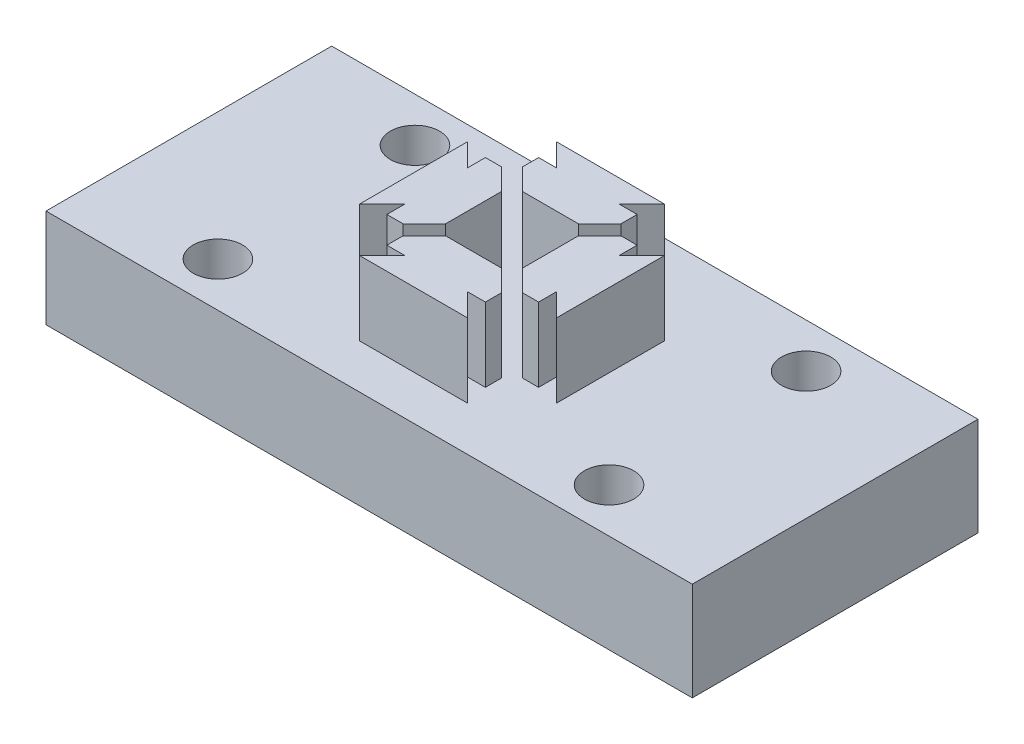
SolidWorks part; units mm, degrees
ref_plane "Front Plane" through (0, 0, 0) normal (0, 0, 1) x (1, 0, 0)
ref_plane "Top Plane" through (0, 0, 0) normal (0, 1, 0) x (1, 0, 0)
ref_plane "Right Plane" through (0, 0, 0) normal (1, 0, 0) x (0, 0, -1)
sketch "Sketch1" plane through (0, 0, 0) normal (0, 1, 0) x (1, 0, 0)
  line L0 (0, 14.5) -> (0, -14.5) construction
  line L1 (-32.8, -14.5) -> (32.8, -14.5)
  line L2 (-32.8, -14.5) -> (-32.8, 14.5)
  line L3 (-32.8, 14.5) -> (32.8, 14.5)
  line L4 (32.8, -14.5) -> (32.8, 14.5)
  line L5 (-32.8, -14.5) -> (32.8, 14.5) construction
  line L6 (-32.8, 14.5) -> (32.8, -14.5) construction
  line L7 (-32.8, 0) -> (32.8, 0) construction
  circle A0 centre (-19.85, 10) radius 2.5
  circle A1 centre (19.85, 10) radius 2.5
  circle A2 centre (19.85, -10) radius 2.5
  circle A3 centre (-19.85, -10) radius 2.5
  point P0 (0, 0)
  dimension "D4" = 5
  dimension "D1" = 65.6
  dimension "D2" = 29
  dimension "D3" = 10
  dimension "D5" = 19.85
  dimension "D6" = 2
  dimension "D7" = 2
extrude "Boss-Extrude1" add sketch "Sketch1" along normal blind 10
sketch "Sketch2" plane through (0, 10, 0) normal (0, 1, 0) x (1, 0, 0)
  line L0 (-10, 0) -> (10, 0) construction
  line L1 (-10, -10) -> (10, -10) construction
  line L2 (-10, -10) -> (-10, 10) construction
  line L3 (-10, 10) -> (10, 10) construction
  line L4 (10, -10) -> (10, 10) construction
  line L5 (-10, -10) -> (10, 10) construction
  line L6 (-10, 10) -> (10, -10) construction
  line L11 (0, 10) -> (0, -10) construction
  line L12 (-10, 5.5) -> (-10, -5.5)
  line L13 (-10, -5.5) -> (-7.7, -3.2)
  line L14 (-7.7, -3.2) -> (-7.7, -5)
  line L15 (-7.7, -5) -> (-6.06, -5)
  line L16 (-6.06, -5) -> (-3.9, -2.84)
  line L17 (-3.9, -2.84) -> (-3.9, 2.84)
  line L18 (-10, 5.5) -> (-7.7, 3.2)
  line L19 (-7.7, 3.2) -> (-7.7, 5)
  line L20 (-7.7, 5) -> (-6.06, 5)
  line L21 (-6.06, 5) -> (-3.9, 2.84)
  point P0 (0, 0)
  point P17 (-10, 0)
  point P25 (-3.9, 0)
  dimension "D1" = 20
  dimension "D2" = 20
  dimension "D3" = 11
  dimension "D4" = 6.4
  dimension "D5" = 5.68
  dimension "D6" = 90
  dimension "D7" = 1.64
  dimension "D8" = 90
  dimension "D9" = 6.1
ref_axis "Axis1" through (0, -0.5, 0) along (0, 1, 0)
extrude "Boss-Extrude2" add sketch "Sketch2" along normal blind 7.5
pattern_circular "CirPattern1" count 4 over 360 about axis through (0, -0.5, 0) along (0, 1, 0) of "Boss-Extrude2"
